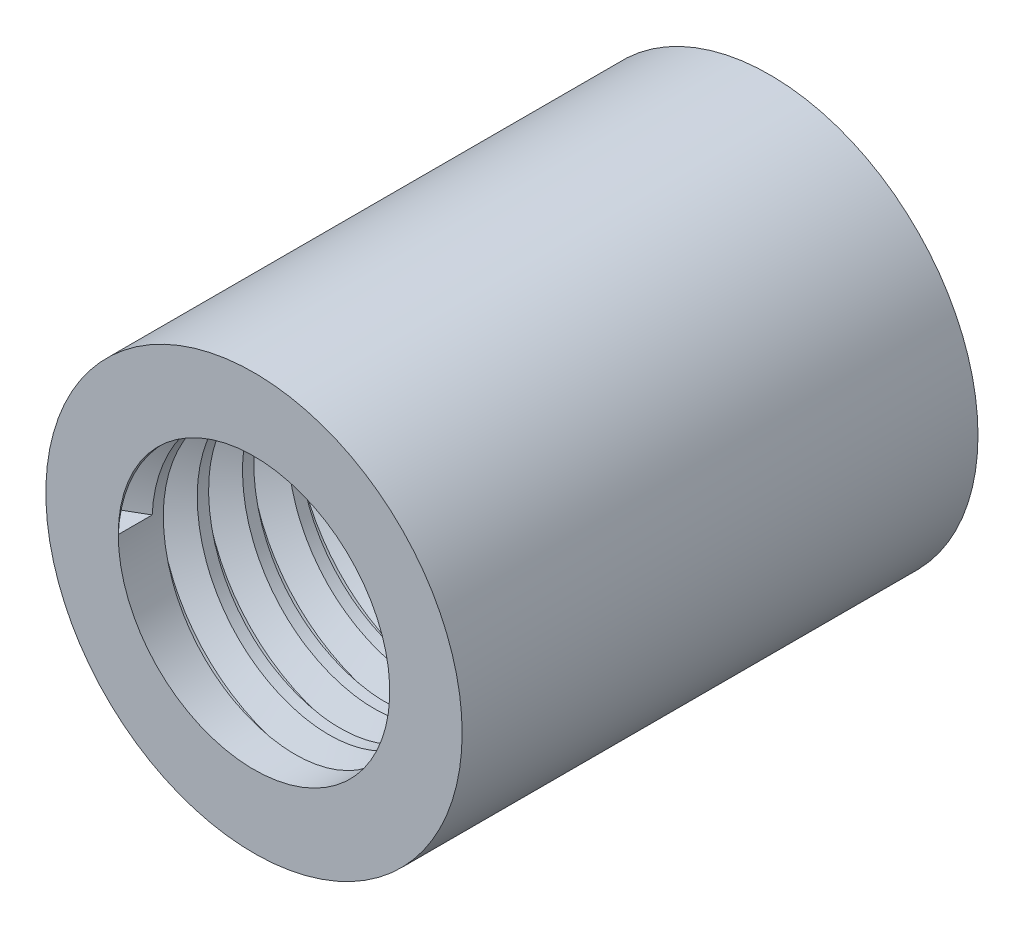
SolidWorks part; units mm, degrees
material "Brass"
ref_plane "Front Plane" through (0, 0, 0) normal (0, 0, 1) x (1, 0, 0)
ref_plane "Top Plane" through (0, 0, 0) normal (0, 1, 0) x (1, 0, 0)
ref_plane "Right Plane" through (0, 0, 0) normal (1, 0, 0) x (0, 0, -1)
sketch "Sketch1" plane through (0, 0, 0) normal (0, 0, 1) x (1, 0, 0)
  circle A0 centre (0, 0) radius 2.3
  circle A1 centre (0, 0) radius 1.5
  dimension "D1" = 3
  dimension "D2" = 4.6
extrude "Boss-Extrude1" add sketch "Sketch1" along normal blind 5.7
thread "Thread1" pitch 0.5 method cut profile "Thread Profile1" start angle 0, offset 0, length 10, pitch 0.5, diameter 3
ref_plane "Plane1" through (-1.5, 0, 5.7) normal (0, -1, 0) x (-1, 0, 0)
sketch "Thread Profile1" plane through (-1.5, 0, 5.7) normal (0, -1, 0) x (-1, 0, 0)
  line L0 (0, 0) -> (0, 0.5) construction
  line L1 (0, 0) -> (0.2706, 0.1562)
  line L2 (0.2706, 0.1562) -> (0.2706, 0.2187)
  line L3 (0.2706, 0.2187) -> (0, 0.375)
  line L4 (0.2706, 0.1875) -> (0, 0.1875) construction
  line L11 (0, 0) -> (0, 0.375)
  point P2 (0, 0)
  dimension "Pitch" = 0.5
  dimension "Profile_Angle" = 60
  dimension "Profile_Land" = 0.0625
  dimension "Profile_Height" = 0.2706
equation "\"OD\"= 4.6"
equation "\"ID\"= 3"
equation "\"D1@Sketch1\"=\"ID\""
equation "\"D2@Sketch1\"=\"OD\""
equation "\"Length\"=5.7"
equation "\"D1@Boss-Extrude1\"=\"Length\""
